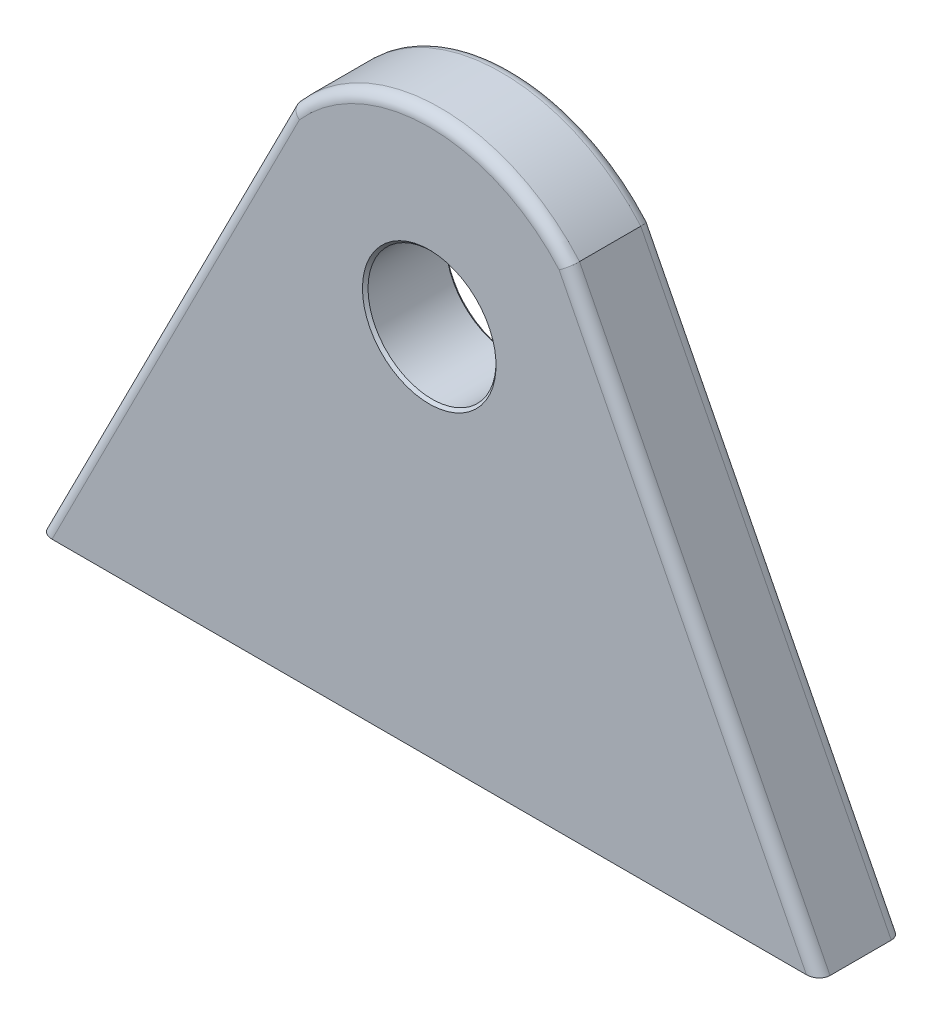
SolidWorks part; units mm, degrees
ref_plane "Front Plane" through (0, 0, 0) normal (0, 0, 1) x (1, 0, 0)
ref_plane "Top Plane" through (0, 0, 0) normal (0, 1, 0) x (1, 0, 0)
ref_plane "Right Plane" through (0, 0, 0) normal (1, 0, 0) x (0, 0, -1)
sketch "Sketch1" plane through (0, 0, 0) normal (0, 0, 1) x (1, 0, 0)
  line L0 (-70, 0) -> (70, 0)
  line L1 (70, 0) -> (25, 88.5829)
  line L2 (-70, 0) -> (-25, 88.5829)
  line L3 (0, 0) -> (0, 110.9918) construction
  arc A1 (-25, 88.5829) -> (25, 88.5829) centre (0, 66.9202) cw
  circle A2 centre (0, 66.9202) radius 11.5
  dimension "D1" = 50
  dimension "D2" = 100
  dimension "D4" = 33.0798
  dimension "D5" = 23
  dimension "D3" = 140
extrude "Boss-Extrude1" add sketch "Sketch1" along normal mid plane 15
fillet "Fillet1" radius 2 6 edges at (-47.5, 44.2914, -7.5) (0, 100, -7.5) (47.5, 44.2914, -7.5) (-47.5, 44.2914, 7.5) (0, 100, 7.5) (47.5, 44.2914, 7.5)
chamfer "Chamfer1" distance 0.5 angle 45 2 edges at (11.5, 66.9202, -7.5) (11.5, 66.9202, 7.5)
